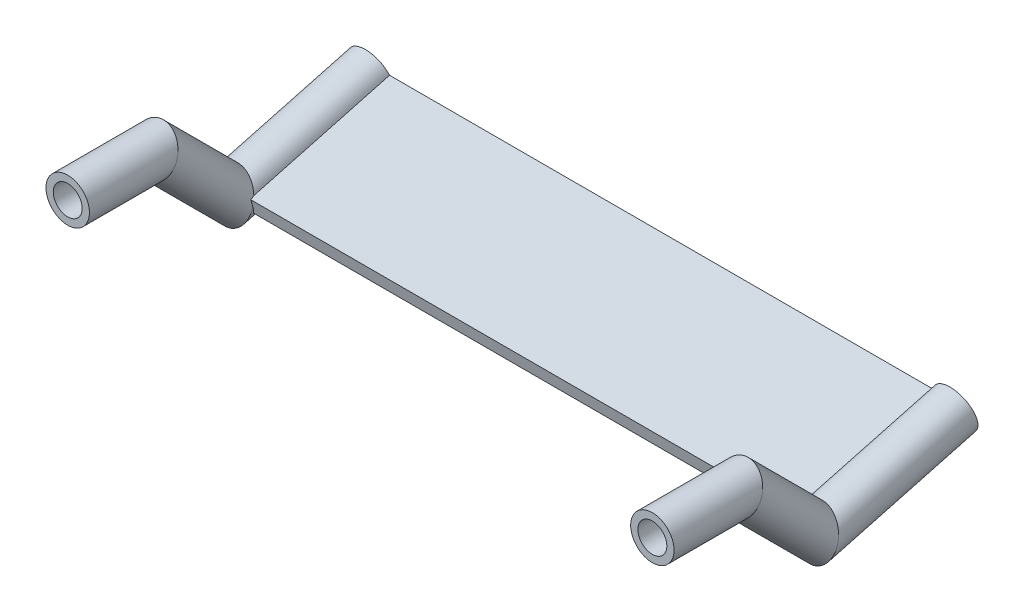
SolidWorks part; units mm, degrees
ref_plane "Front Plane" through (0, 0, 0) normal (0, 0, 1) x (1, 0, 0)
ref_plane "Top Plane" through (0, 0, 0) normal (0, 1, 0) x (1, 0, 0)
ref_plane "Right Plane" through (0, 0, 0) normal (1, 0, 0) x (0, 0, -1)
sketch "Sketch21" plane through (0, 0, 0) normal (1, 0, 0) x (0, 0, -1)
  line L0 (0, 0) -> (120, 0)
  line L1 (120, 0) -> (226.066, -106.066)
  line L2 (226.066, -106.066) -> (419.2512, -54.3022)
  dimension "D1" = 120
  dimension "D2" = 120
  dimension "D3" = 200
sweep "Sweep-Thin1" add path "Sketch21" circular profile diameter 60 parameters "D1"=10, "D3"=60
sketch "Sketch32" plane through (0, 0, 0) normal (1, 0, 0) x (0, 0, -1)
  line L0 (226.066, -106.066) -> (419.2512, -54.3022)
  line L1 (217.1003, -139.5267) -> (235.0318, -72.6054) construction
  line L2 (427.0158, -83.28) -> (411.4866, -25.3244) construction
extrude "Extrude-Thin1" add sketch "Sketch32" along normal blind 760 from offset 20 thin thin type mid plane wall 20
ref_plane "Plane2" through (404.1421, 0, 0) normal (1, 0, 0) x (0, 0, -1)
mirror "Mirror1" about plane through (404.1421, 0, 0) normal (1, 0, 0) of "Sweep-Thin1"
